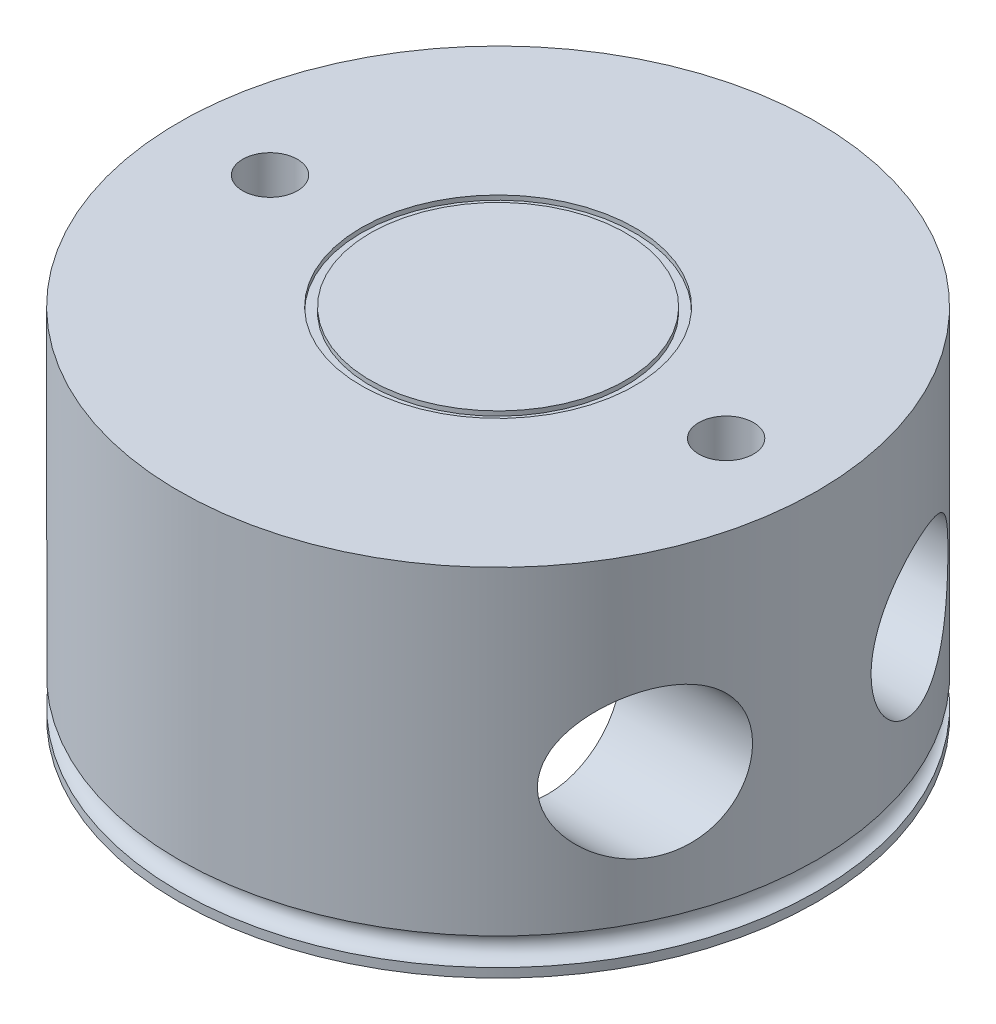
SolidWorks part; units mm, degrees
material "PET"
ref_plane "Front Plane" through (0, 0, 0) normal (0, 0, 1) x (1, 0, 0)
ref_plane "Top Plane" through (0, 0, 0) normal (0, 1, 0) x (1, 0, 0)
ref_plane "Right Plane" through (0, 0, 0) normal (1, 0, 0) x (0, 0, -1)
sketch "Sketch2" plane through (0, 31.8122, 0) normal (0, 1, 0) x (1, 0, 0)
  circle A1 centre (0, 0) radius 33
  circle A2 centre (0, 0) radius 35
  circle A3 centre (0, 0) radius 35
  dimension "D1" = 0
  dimension "D2" = 2
extrude "Boss-Extrude1" add sketch "Sketch2" along normal offset from surface (39 mm away) 4 offset beyond the face yes
sketch "Sketch3" plane through (0, 70.8122, 0) normal (0, 1, 0) x (1, 0, 0)
  circle A2 centre (0, 0) radius 35
  circle A3 centre (0, 0) radius 35
  dimension "D1" = 0
extrude "Boss-Extrude2" add sketch "Sketch3" against normal blind 2
ref_plane "Plane1" through (19.4938, 0, 0.4913) normal (0.9997, 0, 0.0252) x (0.0252, 0, -0.9997)
sketch "Sketch7" plane through (0, 68.8122, 0) normal (0, -1, 0) x (1, 0, 0)
  line L3 (25, 0) -> (0, 0) construction
  line L5 (-25, 0) -> (0, 0) construction
  circle A0 centre (25, 0) radius 1.5
  circle A1 centre (-25, 0) radius 1.5
  circle A2 centre (25, 0) radius 5.5
  circle A6 centre (-25, 0) radius 4
  dimension "D1" = 3
  dimension "D3" = 3
  dimension "D7" = 8
  dimension "D2" = 25
  dimension "D4" = 25
  dimension "D5" = 180
  dimension "D6" = 4
extrude "Boss-Extrude4" add sketch "Sketch7" along normal blind 19
sketch "Sketch8" plane through (0, 70.8122, 0) normal (0, 1, 0) x (1, 0, 0)
  line L0 (0, 0) -> (25, 0) construction
  circle A2 centre (25, 0) radius 3
  circle A3 centre (-25, 0) radius 3
  dimension "D1" = 6
  dimension "D3" = 6
extrude "Cut-Extrude3" cut sketch "Sketch8" against normal blind 15
chamfer "Chamfer1" distance 3 angle 45 1 edges at (-33, 68.8122, 0)
sketch "Sketch9" plane through (0, 70.8122, 0) normal (0, 1, 0) x (1, 0, 0)
  circle A0 centre (0, 0) radius 15
  circle A1 centre (0, 0) radius 14
  dimension "D1" = 30
  dimension "D2" = 1
extrude "Cut-Extrude4" cut sketch "Sketch9" against normal blind 0.5
sketch "Sketch10" plane through (0, 0, 0) normal (0, 0, 1) x (1, 0, 0)
  line L0 (0, 31.8122) -> (0, 76.011) construction
  line L1 (-35, 31.8122) -> (35, 31.8122) construction
  line L4 (35, 31.8122) -> (35, 70.8122)
  line L5 (35, 32.8122) -> (35, 35.8122)
  circle A0 centre (35, 34.3122) radius 1.5
  dimension "D2" = 3
  dimension "D3" = 2.5
  dimension "D1" = 0
revolve "Cut-Revolve1" cut sketch "Sketch10" angle 360 about L0
sketch "Sketch11" plane through (0, 0, 0) normal (1, 0, 0) x (0, 0, -1)
  line L0 (0, 0) -> (0, 70.8122) construction
  line L1 (35, 70.8122) -> (-35, 70.8122) construction
  line L4 (-35, 31.8122) -> (35, 31.8122) construction
  circle A0 centre (14.5, 49.8122) radius 8
  circle A2 centre (-14.5, 49.8122) radius 8
  dimension "D1" = 16
  dimension "D2" = 14.5
  dimension "D3" = 18
extrude "Cut-Extrude5" cut sketch "Sketch11" along normal through all
ref_plane "Plane2" through (20, 0, 0) normal (1, 0, 0) x (0, 0, -1)
sketch "Sketch12" plane through (20, 0, 0) normal (1, 0, 0) x (0, 0, -1)
  line L0 (-24.5, 49.8122) -> (-27.5, 70.8122)
  line L1 (35, 70.8122) -> (-35, 70.8122) construction
  line L2 (-14.5, 49.8122) -> (-14.5, 68.8122) construction
  line L3 (-30, 68.8122) -> (30, 68.8122) construction
  line L4 (0, 49.8122) -> (0, 68.8122) construction
  line L5 (-5.5, 49.8122) -> (5.5, 49.8122) construction
  line L6 (-5.5, 68.8122) -> (5.5, 68.8122) construction
  line L7 (-4.5, 49.8122) -> (-4.5, 70.8122)
  line L9 (24.5, 49.8122) -> (27.5, 70.8122)
  line L10 (4.5, 49.8122) -> (4.5, 70.8122)
  line L12 (-27.5, 70.8122) -> (-4.5, 70.8122)
  line L13 (14, 70.8122) -> (-14, 70.8122) construction
  line L14 (4.5, 70.8122) -> (27.5, 70.8122)
  circle A2 centre (-14.5, 49.8122) radius 8
  circle A3 centre (-14.5, 49.8122) radius 8
  circle A4 centre (-14.5, 49.8122) radius 10
  circle A5 centre (14.5, 49.8122) radius 8
  circle A6 centre (14.5, 49.8122) radius 8
  circle A7 centre (14.5, 49.8122) radius 10
  dimension "D5" = 13
  dimension "D1" = 0
  dimension "D2" = 0
  dimension "D3" = 2
  dimension "D4" = 2
extrude "Boss-Extrude5" add sketch "Sketch12" along normal through all contours A4 L7 L12 L0 | A4 A3 | A7 A6 | A7 L9 L14 L10 region at (20, 64.0243, 15.6769) region at (20, 59.5294, 14.5) region at (20, 64.0243, -15.6769) region at (20, 40.0951, -14.5)
sketch "Sketch13" plane through (0, 70.8122, 0) normal (0, 1, 0) x (1, 0, 0)
  circle A0 centre (0, 0) radius 35
  circle A1 centre (0, 0) radius 55
  dimension "D1" = 20
extrude "Cut-Extrude6" cut sketch "Sketch13" against normal through all
fillet "Fillet1" radius 10 1 edges at (-29, 68.8122, 0)
